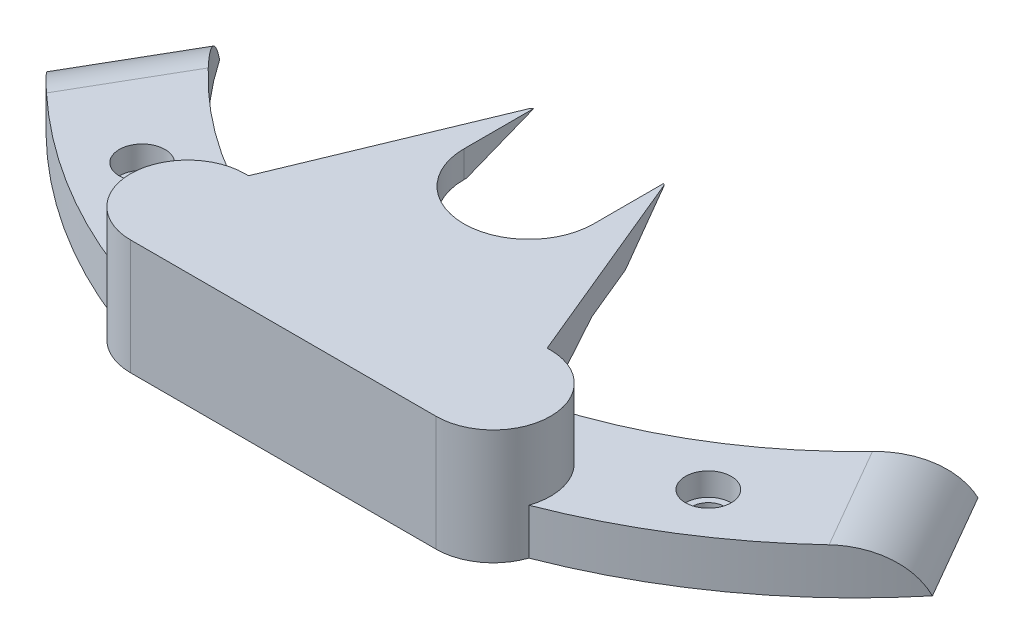
SolidWorks part; units mm, degrees
ref_plane "Front Plane" through (0, 0, 0) normal (0, 0, 1) x (1, 0, 0)
ref_plane "Top Plane" through (0, 0, 0) normal (0, 1, 0) x (1, 0, 0)
ref_plane "Right Plane" through (0, 0, 0) normal (1, 0, 0) x (0, 0, -1)
sketch "Sketch1" plane through (0, 0, 0) normal (0, 1, 0) x (1, 0, 0)
  line L0 (-20, 0) -> (20, 0) construction
  line L1 (-20, 7.5) -> (20, 7.5)
  line L2 (20, -7.5) -> (-20, -7.5)
  circle A0 centre (20, 0) radius 7.5
  circle A1 centre (-20, 0) radius 7.5
  point P4 (0, 0)
  dimension "D1" = 40
  dimension "D2" = 15
extrude "Boss-Extrude1" add sketch "Sketch1" along normal blind 15.07 contours A0 | A1 A0 L1 | A1 L2 A0 | A1 region at (0, 0, 0) region at (-20, 0, 0) region at (20, 0, 0)
ref_plane "Plane1" through (0, 15.07, 0) normal (0, -1, 0) x (-1, 0, 0)
sketch "Sketch3" plane through (0, 15.07, 0) normal (0, -1, 0) x (-1, 0, 0)
  line L0 (0, 0) -> (0, 21.3454) construction
  line L1 (0, 10) -> (0, 7.5) construction
  line L2 (29.0391, 7.5) -> (-29.0391, 7.5)
  line L3 (23.9129, -0.4221) -> (0, 57.3087) construction
  line L4 (-35.3553, 24.6447) -> (35.3553, 24.6447) construction
  line L5 (-35.3553, 24.6447) -> (-35.3553, 95.3553) construction
  line L6 (-35.3553, 95.3553) -> (35.3553, 95.3553) construction
  line L7 (35.3553, 24.6447) -> (35.3553, 95.3553) construction
  line L8 (-35.3553, 24.6447) -> (35.3553, 95.3553) construction
  line L9 (-35.3553, 95.3553) -> (35.3553, 24.6447) construction
  line L10 (0, 57.3087) -> (-24.0511, -0.7557) construction
  line L11 (-8.5, 24.6447) -> (-8.5, 33.8098)
  line L12 (8.5, 24.6447) -> (8.5, 33.8098)
  line L13 (22.989, -0.8048) -> (0, 54.6956)
  line L14 (0, 54.6956) -> (-23.1272, -1.1384)
  circle A0 centre (0, 60) radius 50 construction
  circle A1 centre (0, 24.6447) radius 7.5 construction
  circle A2 centre (0, 24.6447) radius 12.5
  circle A3 centre (0, 24.6447) radius 8.5
  point P2 (0, 10)
  point P4 (0, 10)
  point P27 (18.1786, 13.4217)
  point P28 (-18.1786, 13.4217)
  point P33 (0, 7.5)
  dimension "D2" = 100
  dimension "D3" = 5
  dimension "D5" = 15
  dimension "D4" = 45
  dimension "D6" = 1
  dimension "D7" = 1
extrude "Boss-Extrude3" add sketch "Sketch3" along normal blind 3.5 contours A2 L14 L2 L13 | A3 L11 A2 L14 L13 L12 region at (0, 15.07, -7.9264) region at (0, 15.07, -12.4755)
sketch "Sketch4" plane through (0, 0, 0) normal (1, 0, 0) x (0, 0, -1)
  line L0 (7.5, 11.57) -> (7.5, 8.67)
  line L1 (7.5, 15.07) -> (7.5, 0) construction
  line L2 (7.5, 11.57) -> (17.5, 11.57)
  line L3 (33.5716, 11.57) -> (7.5, 11.57) construction
  line L4 (7.5, 8.67) -> (17.5, 11.57)
  dimension "D1" = 2.9
  dimension "D2" = 10
extrude "Boss-Extrude4" add sketch "Sketch4" along normal blind 26 and the other way blind 27
sketch "Sketch5" plane through (0, 11.57, 0) normal (0, 1, 0) x (1, 0, 0)
  line L0 (-19.5491, 7.5) -> (-15.4069, 17.5) construction
  line L1 (-15.4069, 17.5) -> (-27, 17.5) construction
  line L2 (-27, 17.5) -> (-27, 7.5) construction
  line L3 (-27, 7.5) -> (-20, 7.5) construction
  line L4 (-20, 7.5) -> (-19.5491, 7.5) construction
  line L5 (15.4069, 17.5) -> (19.5491, 7.5) construction
  line L6 (19.5491, 7.5) -> (20, 7.5) construction
  line L7 (20, 7.5) -> (26, 7.5) construction
  line L8 (26, 7.5) -> (26, 17.5) construction
  line L9 (26, 17.5) -> (15.4069, 17.5) construction
  line L10 (-19.5491, 7.5) -> (-15.4069, 17.5)
  line L11 (-15.4069, 17.5) -> (-27, 17.5)
  line L12 (-27, 17.5) -> (-27, 7.5)
  line L13 (-27, 7.5) -> (-20, 7.5)
  line L14 (-20, 7.5) -> (-19.5491, 7.5)
  line L15 (15.4069, 17.5) -> (19.5491, 7.5)
  line L16 (19.5491, 7.5) -> (20, 7.5)
  line L17 (20, 7.5) -> (26, 7.5)
  line L18 (26, 7.5) -> (26, 17.5)
  line L19 (26, 17.5) -> (15.4069, 17.5)
  line L21 (4.6048, 17.5) -> (-4.6048, 17.5)
  line L22 (4.6048, 17.5) -> (-4.6048, 17.5)
  arc A1 (-4.6048, 17.5) -> (4.6048, 17.5) centre (0, 24.6447) ccw
  arc A3 (-4.6048, 17.5) -> (4.6048, 17.5) centre (0, 24.6447) ccw
  dimension "D1" = 0
extrude "Cut-Extrude1" cut sketch "Sketch5" against normal through all both
sketch "Sketch6" plane through (0, 0, 0) normal (1, 0, 0) x (0, 0, -1)
  line L0 (25, 11.57) -> (33.8098, 15.07)
  line L1 (33.8098, 15.07) -> (25, 15.07)
  line L2 (33.5716, 15.07) -> (7.5, 15.07) construction
  line L3 (25, 15.07) -> (25, 11.57)
  line L4 (25, 11.57) -> (32.5042, 6.0383)
  line L5 (32.5042, 6.0383) -> (33.8098, 8.1469)
  line L6 (33.8098, 8.1469) -> (33.8098, 15.07)
  line L7 (17.5, 11.57) -> (17.5, 17.5325) construction
  line L8 (25, 15.07) -> (17.5, 15.07)
  line L9 (33.5716, 11.57) -> (17.5, 11.57) construction
  dimension "D1" = 7.5
extrude "Cut-Extrude2" cut sketch "Sketch6" against normal through all both and the other way through all contours L5 L6 L0 L4 region at (0, 10.77, -30.7539)
sketch "Sketch7" plane through (0, 0, 0) normal (0, 1, 0) x (1, 0, 0)
  line L0 (-1.0996, -7.5) -> (1.0996, -7.5)
  line L1 (20, -7.5) -> (-20, -7.5) construction
  line L2 (49.6485, 33.8098) -> (57.7945, 19.7005)
  line L3 (0, 67.5) -> (0, 57.5141) construction
  line L4 (8.5, 33.8098) -> (49.6485, 33.8098) construction
  line L5 (-49.6485, 33.8098) -> (-57.7945, 19.7005)
  circle A0 centre (0, 67.5) radius 75
  circle A1 centre (0, 67.5) radius 60
  point P7 (0, -7.5)
  dimension "D1" = 150
  dimension "D3" = 30
  dimension "D2" = 15
extrude "Boss-Extrude5" add sketch "Sketch7" along normal blind 6 contours A1 L5 A0 L2 region at (52.6585, 0, -26.1414)
fillet "Fillet1" radius 10 2 edges at (-53.7215, 6, -26.7551) (53.7215, 6, -26.7551)
sketch "Sketch8" plane through (0, 6, 0) normal (0, 1, 0) x (1, 0, 0)
  line L0 (33.2234, 17.538) -> (40.9053, 4.637) construction
  line L1 (26.7689, 2.7316) -> (47.3599, 19.4434) construction
  line L2 (51.2363, 12.7292) -> (43.4834, 26.1577) construction
  line L3 (0, -55) -> (0, 55) construction
  arc A0 (0, 7.5) -> (43.4834, 26.1577) centre (0, 67.5) ccw construction
  arc A1 (27.0936, -2.4352) -> (51.2363, 12.7292) centre (0, 67.5) ccw construction
  circle A2 centre (37.0644, 11.0875) radius 2.15
  circle A3 centre (37.0644, 11.0875) radius 3
  circle A4 centre (-37.0644, 11.0875) radius 2.15
  circle A5 centre (-37.0644, 11.0875) radius 3
  point P12 (37.0644, 11.0875)
  dimension "D1" = 0.85
  dimension "D2" = 4.3
extrude "Cut-Extrude3" cut sketch "Sketch8" against normal through all contours A2 | A4 region at (37.0644, 6, -11.0875)
extrude "Cut-Extrude4" cut sketch "Sketch8<4>" against normal blind 3
sketch "Sketch8<4>" plane through (0, 6, 0) normal (0, 1, 0) x (1, 0, 0) same geometry as "Sketch8"
